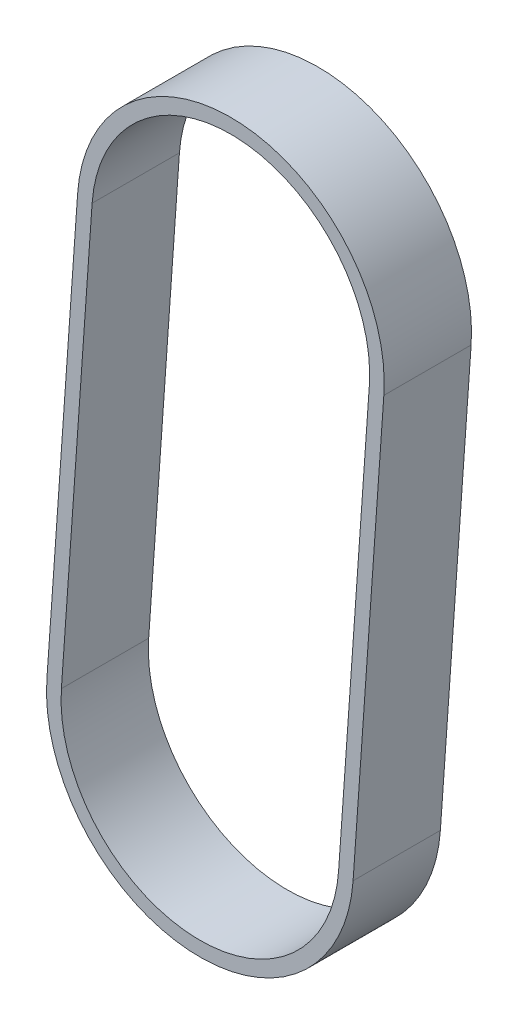
SolidWorks part; units mm, degrees
ref_plane "Front Plane" through (0, 0, 0) normal (0, 0, 1) x (1, 0, 0)
ref_plane "Top Plane" through (0, 0, 0) normal (0, 1, 0) x (1, 0, 0)
ref_plane "Right Plane" through (0, 0, 0) normal (1, 0, 0) x (0, 0, -1)
sketch "Sketch2" plane through (0, 0, 0) normal (0, 0, 1) x (1, 0, 0)
  line L0 (0, 0) -> (1, 0) construction
  line L1 (0, 0) -> (0, 1) construction
  line L4 (-17.4574, -43.9121) -> (-14.2884, 1.008)
  line L5 (14.2884, -1.008) -> (11.1195, -45.9281)
  arc A2 (11.1195, -45.9281) -> (-17.4574, -43.9121) centre (-3.1689, -44.9201) cw
  arc A3 (-14.2884, 1.008) -> (14.2884, -1.008) centre (0, 0) cw
extrude "Extrude-Thin1" add sketch "Sketch2" along normal blind 9 thin thin type one direction wall 1.5
